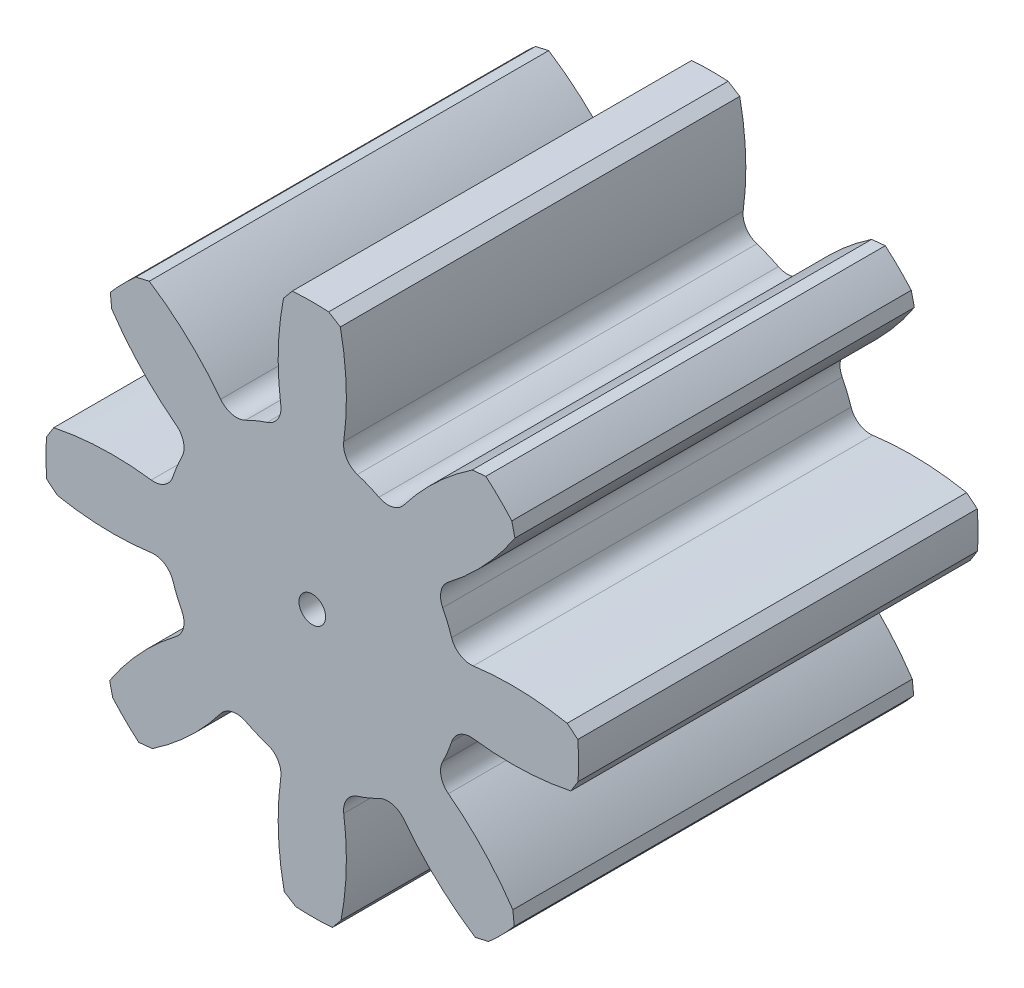
SolidWorks part; units mm, degrees
ref_plane "Front Plane" through (0, 0, 0) normal (0, 0, 1) x (1, 0, 0)
ref_plane "Top Plane" through (0, 0, 0) normal (0, 1, 0) x (1, 0, 0)
ref_plane "Right Plane" through (0, 0, 0) normal (1, 0, 0) x (0, 0, -1)
sketch "Sketch1" plane through (0, 0, 0) normal (0, 0, 1) x (1, 0, 0)
  line L0 (0, 0) -> (0, 10) construction
  line L1 (1.9509, 9.8079) -> (0, 0) construction
  line L2 (3.8268, 9.2388) -> (0, 0) construction
  circle A0 centre (0, 0) radius 10
  circle A1 centre (0, 0) radius 5.5
  circle A2 centre (0, 0) radius 8
  arc A3 (1, 9.9499) -> (1.073, 5.3943) centre (-9.5272, 7.5028) cw
  arc A4 (-1, 9.9499) -> (-1.073, 5.3943) centre (9.5272, 7.5028) ccw
  arc A5 (7.7427, 6.3285) -> (4.5731, 3.0556) centre (-1.4314, 12.042) cw
  arc A6 (6.3285, 7.7427) -> (3.0556, 4.5731) centre (12.042, -1.4314) ccw
  arc A7 (9.9499, -1) -> (5.3943, -1.073) centre (7.5028, 9.5272) cw
  arc A8 (9.9499, 1) -> (5.3943, 1.073) centre (7.5028, -9.5272) ccw
  arc A9 (6.3285, -7.7427) -> (3.0556, -4.5731) centre (12.042, 1.4314) cw
  arc A10 (7.7427, -6.3285) -> (4.5731, -3.0556) centre (-1.4314, -12.042) ccw
  arc A11 (-1, -9.9499) -> (-1.073, -5.3943) centre (9.5272, -7.5028) cw
  arc A12 (1, -9.9499) -> (1.073, -5.3943) centre (-9.5272, -7.5028) ccw
  arc A13 (-7.7427, -6.3285) -> (-4.5731, -3.0556) centre (1.4314, -12.042) cw
  arc A14 (-6.3285, -7.7427) -> (-3.0556, -4.5731) centre (-12.042, 1.4314) ccw
  arc A15 (-9.9499, 1) -> (-5.3943, 1.073) centre (-7.5028, -9.5272) cw
  arc A16 (-9.9499, -1) -> (-5.3943, -1.073) centre (-7.5028, 9.5272) ccw
  arc A17 (-6.3285, 7.7427) -> (-3.0556, 4.5731) centre (-12.042, -1.4314) cw
  arc A18 (-7.7427, 6.3285) -> (-4.5731, 3.0556) centre (1.4314, 12.042) ccw
  circle A19 centre (0, 0) radius 0.5
  dimension "D1" = 16
  dimension "D2" = 2
  dimension "D3" = 2.5
  dimension "D8" = 1
  dimension "D4" = 22.5
  dimension "D5" = 11.25
  dimension "D6" = 1
  dimension "D7" = 8
extrude "Boss-Extrude1" add sketch "Sketch1" along normal blind 15 contours A2 A18 A1 A17 | A1 | A0 A18 A2 A17 | A2 A4 A1 A3 | A0 A4 A2 A3 | A2 A6 A1 A5 | A0 A6 A2 A5 | A2 A8 A1 A7 | A0 A8 A2 A7 | A2 A10 A1 A9 | A0 A10 A2 A9 | A0 A12 A2 A11 | A2 A12 A1 A11 | A0 A14 A2 A13 | A2 A14 A1 A13 | A2 A16 A1 A15 | A0 A16 A2 A15 region at (8.9344, 0, 0) region at (6.3176, 6.3176, 0) region at (6.7465, 0, 0) region at (6.3176, -6.3176, 0) region at (4.7705, 4.7705, 0) region at (5.3187, 0.5238, 0) region at (4.7705, -4.7705, 0) region at (0, 8.9344, 0) region at (0, -8.9344, 0) region at (0, 6.7465, 0) region at (0, -6.7465, 0) region at (-6.3176, 6.3176, 0) region at (-6.3176, -6.3176, 0) region at (-4.7705, 4.7705, 0) region at (-4.7705, -4.7705, 0) region at (-8.9344, 0, 0) region at (-6.7465, 0, 0)
fillet "Fillet1" radius 0.75 16 edges at (4.5731, -3.0556, 7.5) (4.5731, 3.0556, 7.5) (5.3943, 1.073, 7.5) (5.3943, -1.073, 7.5) (3.0556, -4.5731, 7.5) (1.073, -5.3943, 7.5) (-1.073, -5.3943, 7.5) (-3.0556, -4.5731, 7.5) (-4.5731, -3.0556, 7.5) (-5.3943, -1.073, 7.5) (-5.3943, 1.073, 7.5) (-4.5731, 3.0556, 7.5) (-1.073, 5.3943, 7.5) (-3.0556, 4.5731, 7.5) (3.0556, 4.5731, 7.5) (1.073, 5.3943, 7.5)
chamfer "Chamfer1" distance 0.25 angle 45 16 edges at (-1, 9.9499, 7.5) (1, 9.9499, 7.5) (6.3285, 7.7427, 7.5) (7.7427, 6.3285, 7.5) (9.9499, 1, 7.5) (9.9499, -1, 7.5) (7.7427, -6.3285, 7.5) (6.3285, -7.7427, 7.5) (1, -9.9499, 7.5) (-1, -9.9499, 7.5) (-6.3285, -7.7427, 7.5) (-7.7427, -6.3285, 7.5) (-9.9499, -1, 7.5) (-9.9499, 1, 7.5) (-7.7427, 6.3285, 7.5) (-6.3285, 7.7427, 7.5) first distance on face at (0, 9.9749, 7.5) first distance on face at (1.18, 8.0026, 7.5) first distance on face at (7.0533, 7.0533, 7.5) first distance on face at (6.4931, 4.8243, 7.5) first distance on face at (9.9749, 0, 7.5) first distance on face at (8.0026, -1.18, 7.5) first distance on face at (7.0533, -7.0533, 7.5) first distance on face at (4.8243, -6.4931, 7.5) first distance on face at (0, -9.9749, 7.5) first distance on face at (-1.18, -8.0026, 7.5) first distance on face at (-7.0533, -7.0533, 7.5) first distance on face at (-6.4931, -4.8243, 7.5) first distance on face at (-9.9749, 0, 7.5) first distance on face at (-8.0026, 1.18, 7.5) first distance on face at (-7.0533, 7.0533, 7.5) first distance on face at (-4.8243, 6.4931, 7.5)
